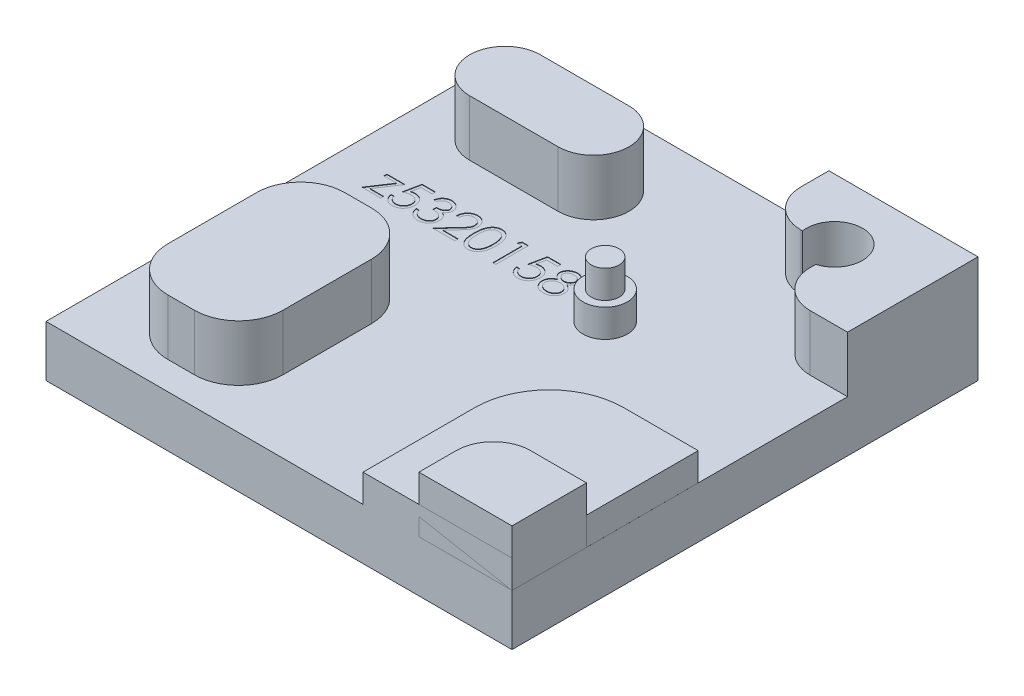
SolidWorks part; units mm, degrees
material "Alumina"
ref_plane "Front Plane" through (0, 0, 0) normal (0, 0, 1) x (1, 0, 0)
ref_plane "Top Plane" through (0, 0, 0) normal (0, 1, 0) x (1, 0, 0)
ref_plane "Right Plane" through (0, 0, 0) normal (1, 0, 0) x (0, 0, -1)
sketch "Sketch1" plane through (0, 0, 0) normal (0, 1, 0) x (1, 0, 0)
  line L1 (-22.6457, 20.9641) -> (27.3543, 20.9641)
  line L2 (-22.6457, 20.9641) -> (-22.6457, -29.0359)
  line L3 (-22.6457, -29.0359) -> (27.3543, -29.0359)
  line L4 (27.3543, 20.9641) -> (27.3543, -29.0359)
  dimension "D1" = 50
  dimension "D2" = 50
extrude "Boss-Extrude4" add sketch "Sketch1" along normal blind 5.5 contours L2 L3 L4 L1
sketch "Sketch5" plane through (0, 5.5, 0) normal (0, 1, 0) x (1, 0, 0)
  line L0 (17.3643, -29.0359) -> (17.3643, -25.0399)
  line L2 (21.3603, -21.0439) -> (27.3543, -21.0439)
  line L14 (17.3643, -29.0359) -> (27.3543, -29.0359)
  line L15 (27.3543, -29.0359) -> (27.3543, -21.0439)
  arc A0 (21.3603, -21.0439) -> (17.3643, -25.0399) centre (21.3603, -25.0399) ccw
sketch "Sketch6" plane through (0, 5.5, 0) normal (0, 1, 0) x (1, 0, 0)
  line L0 (11.3682, -29.0359) -> (11.3682, -17.0479)
  line L2 (19.3602, -9.0559) -> (27.3522, -9.0559)
  line L18 (27.3522, -29.0359) -> (27.3522, -9.0559)
  line L21 (11.3682, -29.0359) -> (27.3522, -29.0359)
  arc A0 (19.3602, -9.0559) -> (11.3682, -17.0479) centre (19.3602, -17.0479) ccw
sketch "Sketch7" plane through (0, 5.5, 0) normal (0, 1, 0) x (1, 0, 0)
  line L0 (-11.1457, -6.5359) -> (-11.1457, -26.5359) construction
  line L1 (-12.5707, -7.0359) -> (-9.7207, -7.0359)
  line L2 (-17.3207, -11.7859) -> (-17.3207, -21.2859)
  line L3 (-12.5707, -26.0359) -> (-9.7207, -26.0359)
  line L4 (-4.9707, -11.7859) -> (-4.9707, -21.2859)
  line L6 (-17.6457, -16.5359) -> (-4.6457, -16.5359) construction
  arc A0 (-12.5707, -26.0359) -> (-17.3207, -21.2859) centre (-12.5707, -21.2859) cw
  arc A1 (-9.7207, -26.0359) -> (-4.9707, -21.2859) centre (-9.7207, -21.2859) ccw
  arc A2 (-4.9707, -11.7859) -> (-9.7207, -7.0359) centre (-9.7207, -11.7859) ccw
  arc A3 (-12.5707, -7.0359) -> (-17.3207, -11.7859) centre (-12.5707, -11.7859) ccw
sketch "Sketch8" plane through (0, 5.5, 0) normal (0, 1, 0) x (1, 0, 0)
  line L0 (15.3543, 13.9641) -> (15.5333, 13.9641)
  line L1 (-15.1457, 16.4641) -> (-5.1457, 16.4641)
  line L3 (-15.1457, 8.4641) -> (-5.1457, 8.4641)
  line L4 (-22.6457, 20.9641) -> (27.3543, 20.9641) construction
  line L5 (-22.6457, 20.9641) -> (-22.6457, -29.0359) construction
  line L6 (11.3543, 20.9641) -> (11.3543, 17.9641)
  line L7 (27.3543, 20.9641) -> (27.3543, -29.0359) construction
  line L8 (19.3543, 11.5557) -> (19.3543, 10.9641)
  line L9 (23.3543, 6.9641) -> (27.3543, 6.9641)
  arc A0 (-5.1457, 16.4641) -> (-5.1457, 8.4641) centre (-5.1457, 12.4641) cw
  arc A1 (-15.1457, 16.4641) -> (-15.1457, 8.4641) centre (-15.1457, 12.4641) ccw
  arc A2 (11.3543, 17.9641) -> (15.3543, 13.9641) centre (15.3543, 17.9641) ccw
  arc A3 (19.3543, 10.9641) -> (23.3543, 6.9641) centre (23.3543, 10.9641) ccw
  arc A4 (15.5333, 13.9641) -> (19.3543, 11.5557) centre (18.4969, 14.4305) cw
  line M8 (27.3543, -29.0359) -> (27.3543, 20.9641)
  line M9 (27.3543, 20.9641) -> (-22.6457, 20.9641)
  dimension "D5" = 14
  dimension "D9" = 8
  dimension "D10" = 4
  dimension "D7" = 3
  dimension "D11" = 4
  dimension "D1" = 8
  dimension "D2" = 10
  dimension "D3" = 4.5
  dimension "D4" = 7.5
  dimension "D6" = 16
  dimension "D8" = 7
sketch "Sketch9" plane through (0, 5.5, 0) normal (0, 1, 0) x (1, 0, 0)
  line L0 (-19.1457, 12.4641) -> (-1.1457, 12.4641) construction
  line L1 (-14.8957, 16.2641) -> (-5.3957, 16.2641)
  line L3 (-14.8957, 8.6641) -> (-5.3957, 8.6641)
  line L5 (-10.1457, 16.4641) -> (-10.1457, 8.4641) construction
  arc A0 (-5.3957, 16.2641) -> (-5.3957, 8.6641) centre (-5.3957, 12.4641) cw
  arc A1 (-14.8957, 16.2641) -> (-14.8957, 8.6641) centre (-14.8957, 12.4641) ccw
sketch "Sketch10" plane through (0, 5.5, 0) normal (0, 1, 0) x (1, 0, 0)
  circle A0 centre (7.3543, 0.9641) radius 2.375
extrude "Boss-Extrude27" add sketch "Sketch8" along normal blind 6 contours L0 A4 L8 A3 L9 L6 A2 M8 M9 region at (12.6762, 5.5, -15.286)
extrude "Boss-Extrude29" add sketch "Sketch10" along normal blind 3 separate body contours A0
sketch "Sketch12" plane through (0, 8.5, 0) normal (0, 1, 0) x (1, 0, 0)
  circle A0 centre (7.3543, 0.9641) radius 1.4985
sketch "Sketch13" plane through (0, 5.5, 0) normal (0, 1, 0) x (1, 0, 0)
  text T0 "z5320158"
extrude "Cut-Extrude1" cut sketch "Sketch13" against normal blind 0.05
extrude "Boss-Extrude31" add sketch "Sketch7" along normal blind 6 separate body contours L2 A0 L3 A1 L4 A2 L1 A3
extrude "Boss-Extrude32" add sketch "Sketch9" along normal blind 6 contours L3 A0 L1 A1
extrude "Boss-Extrude38" add sketch "Sketch6" along normal blind 3 contours L0 A0 L2 L18 L21
extrude "Boss-Extrude39" add sketch "Sketch5" along normal blind 6 separate body contours A0 L0 L14 L15 L2
extrude "Boss-Extrude40" add sketch "Sketch12" along normal blind 3 contours A0
